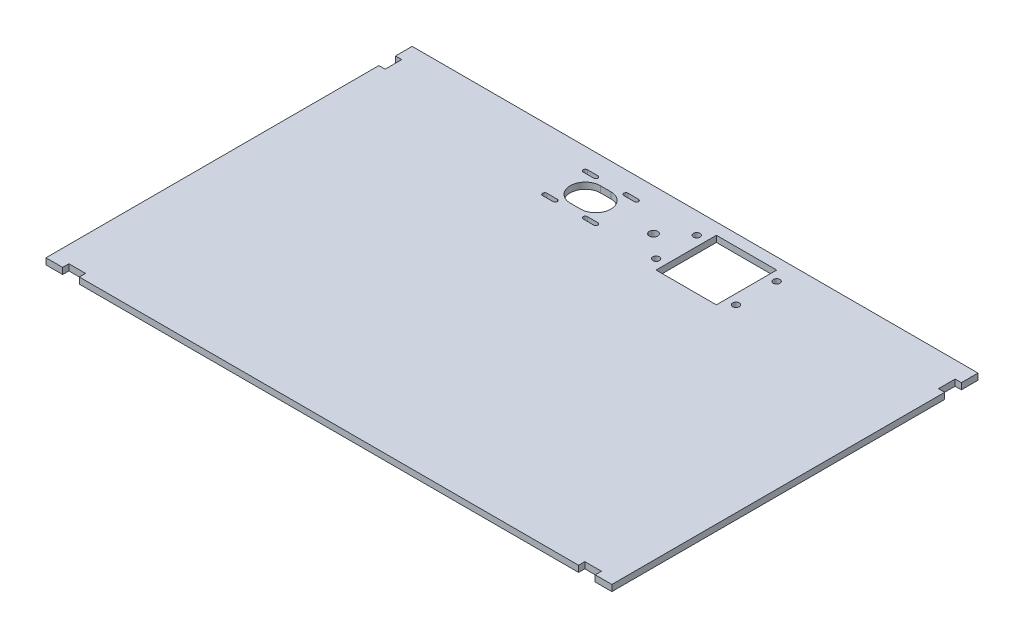
SolidWorks part; units mm, degrees
ref_plane "Front" through (0, 0, 0) normal (0, 0, 1) x (1, 0, 0)
ref_plane "Top" through (0, 0, 0) normal (0, 1, 0) x (1, 0, 0)
ref_plane "Right" through (0, 0, 0) normal (1, 0, 0) x (0, 0, -1)
sketch "Sketch1" plane through (0, 0, 0) normal (0, 1, 0) x (1, 0, 0)
  line L0 (215.9, 247.65) -> (215.9, 279.4) construction
  line L1 (0, 0) -> (12.7, 0)
  line L2 (0, 0) -> (0, 254)
  line L3 (0, 279.4) -> (431.8, 279.4)
  line L4 (431.8, 0) -> (431.8, 254)
  line L5 (148.394, 263.15) -> (156.394, 263.15) construction
  line L6 (148.394, 264.75) -> (156.394, 264.75)
  line L7 (0, 254) -> (4.7625, 254)
  line L8 (431.8, 266.7) -> (427.0375, 266.7)
  line L10 (431.8, 254) -> (427.0375, 254)
  line L11 (427.0375, 266.7) -> (427.0375, 254)
  line L12 (4.7625, 266.7) -> (4.7625, 254)
  line L13 (0, 266.7) -> (4.7625, 266.7)
  line L15 (431.8, 266.7) -> (431.8, 279.4)
  line L16 (0, 266.7) -> (0, 279.4)
  line L17 (25.4, 0) -> (406.4, 0)
  line L19 (12.7, 0) -> (12.7, 4.7625)
  line L20 (12.7, 4.7625) -> (25.4, 4.7625)
  line L21 (25.4, 0) -> (25.4, 4.7625)
  line L22 (406.4, 0) -> (406.4, 4.7625)
  line L23 (419.1, 4.7625) -> (406.4, 4.7625)
  line L24 (419.1, 0) -> (419.1, 4.7625)
  line L25 (419.1, 0) -> (431.8, 0)
  line L26 (167.894, 247.65) -> (215.9, 247.65) construction
  line L27 (152.394, 263.15) -> (183.394, 263.15) construction
  line L28 (152.394, 263.15) -> (152.394, 232.15) construction
  line L29 (152.394, 232.15) -> (183.394, 232.15) construction
  line L30 (183.394, 263.15) -> (183.394, 232.15) construction
  line L31 (152.394, 263.15) -> (183.394, 232.15) construction
  line L32 (152.394, 232.15) -> (183.394, 263.15) construction
  line L33 (248.406, 263.15) -> (279.406, 263.15) construction
  line L34 (248.406, 263.15) -> (248.406, 232.15) construction
  line L35 (248.406, 232.15) -> (279.406, 232.15) construction
  line L36 (279.406, 263.15) -> (279.406, 232.15) construction
  line L37 (248.406, 263.15) -> (279.406, 232.15) construction
  line L38 (248.406, 232.15) -> (279.406, 263.15) construction
  line L39 (215.9, 247.65) -> (263.906, 247.65) construction
  line L40 (148.394, 261.55) -> (156.394, 261.55)
  line L41 (179.394, 263.15) -> (187.394, 263.15) construction
  line L42 (179.394, 264.75) -> (187.394, 264.75)
  line L43 (179.394, 261.55) -> (187.394, 261.55)
  line L44 (148.394, 232.15) -> (156.394, 232.15) construction
  line L45 (148.394, 233.75) -> (156.394, 233.75)
  line L46 (148.394, 230.55) -> (156.394, 230.55)
  line L47 (179.394, 232.15) -> (187.394, 232.15) construction
  line L48 (179.394, 233.75) -> (187.394, 233.75)
  line L49 (179.394, 230.55) -> (187.394, 230.55)
  line L50 (244.406, 263.15) -> (252.406, 263.15) construction
  line L51 (244.406, 264.75) -> (252.406, 264.75)
  line L52 (244.406, 261.55) -> (252.406, 261.55)
  line L53 (244.406, 232.15) -> (252.406, 232.15) construction
  line L54 (244.406, 233.75) -> (252.406, 233.75)
  line L55 (244.406, 230.55) -> (252.406, 230.55)
  line L56 (275.406, 232.15) -> (283.406, 232.15) construction
  line L57 (275.406, 233.75) -> (283.406, 233.75)
  line L58 (275.406, 230.55) -> (283.406, 230.55)
  line L59 (283.406, 263.15) -> (275.406, 263.15) construction
  line L60 (283.406, 261.55) -> (275.406, 261.55)
  line L61 (283.406, 264.75) -> (275.406, 264.75)
  line L62 (163.894, 247.65) -> (171.894, 247.65) construction
  line L63 (163.894, 259.15) -> (171.894, 259.15)
  line L64 (163.894, 236.15) -> (171.894, 236.15)
  line L65 (259.906, 247.65) -> (267.906, 247.65) construction
  line L66 (259.906, 259.15) -> (267.906, 259.15)
  line L67 (259.906, 236.15) -> (267.906, 236.15)
  circle A0 centre (215.9, 247.65) radius 3.175
  arc A12 (148.394, 264.75) -> (148.394, 261.55) centre (148.394, 263.15) ccw
  arc A13 (156.394, 261.55) -> (156.394, 264.75) centre (156.394, 263.15) ccw
  arc A14 (179.394, 264.75) -> (179.394, 261.55) centre (179.394, 263.15) ccw
  arc A15 (187.394, 261.55) -> (187.394, 264.75) centre (187.394, 263.15) ccw
  arc A16 (148.394, 233.75) -> (148.394, 230.55) centre (148.394, 232.15) ccw
  arc A17 (156.394, 230.55) -> (156.394, 233.75) centre (156.394, 232.15) ccw
  arc A18 (179.394, 233.75) -> (179.394, 230.55) centre (179.394, 232.15) ccw
  arc A19 (187.394, 230.55) -> (187.394, 233.75) centre (187.394, 232.15) ccw
  arc A20 (244.406, 264.75) -> (244.406, 261.55) centre (244.406, 263.15) ccw
  arc A21 (252.406, 261.55) -> (252.406, 264.75) centre (252.406, 263.15) ccw
  arc A22 (244.406, 233.75) -> (244.406, 230.55) centre (244.406, 232.15) ccw
  arc A23 (252.406, 230.55) -> (252.406, 233.75) centre (252.406, 232.15) ccw
  arc A24 (275.406, 233.75) -> (275.406, 230.55) centre (275.406, 232.15) ccw
  arc A25 (283.406, 230.55) -> (283.406, 233.75) centre (283.406, 232.15) ccw
  arc A26 (283.406, 261.55) -> (283.406, 264.75) centre (283.406, 263.15) ccw
  arc A27 (275.406, 264.75) -> (275.406, 261.55) centre (275.406, 263.15) ccw
  arc A28 (163.894, 259.15) -> (163.894, 236.15) centre (163.894, 247.65) ccw
  arc A29 (171.894, 236.15) -> (171.894, 259.15) centre (171.894, 247.65) ccw
  arc A30 (259.906, 259.15) -> (259.906, 236.15) centre (259.906, 247.65) ccw
  arc A31 (267.906, 236.15) -> (267.906, 259.15) centre (267.906, 247.65) ccw
  point P19 (183.394, 263.15)
  point P24 (152.394, 263.15)
  point P32 (248.406, 232.15)
  point P44 (12.7, 2.3813)
  point P57 (152.394, 232.15)
  point P64 (183.394, 232.15)
  point P70 (248.406, 263.15)
  point P80 (279.406, 232.15)
  point P87 (279.406, 263.15)
  point P95 (167.894, 247.65)
  point P100 (263.906, 247.65)
  dimension "D4" = 6.35
  dimension "D5" = 1.6
  dimension "D10" = 4
  dimension "D3" = 31.75
  dimension "D9" = 11.5
  dimension "D1" = 279.4
  dimension "D2" = 431.8
  dimension "D6" = 48.006
  dimension "D7" = 48.006
  dimension "D8" = 31
  dimension "D11" = 4
  dimension "D12" = 4.7625
  dimension "D13" = 12.7
  dimension "D14" = 12.7
  dimension "D15" = 4.7625
  dimension "D16" = 12.7
  dimension "D17" = 12.7
extrude "Boss-Extrude1" add sketch "Sketch1" along normal blind 4.7625
sketch "Sketch5" plane through (0, 4.7625, 0) normal (0, 1, 0) x (1, 0, 0)
  line L0 (263.906, 259.15) -> (263.906, 236.15) construction
  line L5 (267.906, 259.15) -> (259.906, 259.15) construction
  line L6 (259.906, 236.15) -> (267.906, 236.15) construction
  line L7 (248.406, 247.65) -> (279.406, 247.65) construction
  line L8 (233.426, 232.15) -> (254.006, 232.15) construction
  line L9 (240.906, 224.65) -> (286.906, 224.65)
  line L10 (240.906, 224.65) -> (240.906, 270.65)
  line L11 (240.906, 270.65) -> (286.906, 270.65)
  line L12 (286.906, 224.65) -> (286.906, 270.65)
  line L13 (240.906, 224.65) -> (286.906, 270.65) construction
  line L14 (240.906, 270.65) -> (286.906, 224.65) construction
  line L15 (254.006, 263.15) -> (233.426, 263.15) construction
  line L17 (225.806, 224.536) -> (302.006, 224.536) construction
  line L18 (225.806, 224.536) -> (225.806, 270.764) construction
  line L19 (225.806, 270.764) -> (302.006, 270.764) construction
  line L20 (302.006, 224.536) -> (302.006, 270.764) construction
  line L21 (225.806, 224.536) -> (302.006, 270.764) construction
  line L22 (225.806, 270.764) -> (302.006, 224.536) construction
  arc A0 (259.906, 259.15) -> (259.906, 236.15) centre (259.906, 247.65) ccw construction
  arc A1 (267.906, 236.15) -> (267.906, 259.15) centre (267.906, 247.65) ccw construction
  circle A2 centre (233.426, 263.15) radius 2.54
  circle A3 centre (294.386, 263.15) radius 2.54
  circle A4 centre (233.426, 232.15) radius 2.54
  circle A5 centre (294.386, 232.15) radius 2.54
  arc A7 (252.406, 230.55) -> (252.406, 233.75) centre (252.406, 232.15) ccw construction
  arc A8 (252.406, 261.55) -> (252.406, 264.75) centre (252.406, 263.15) ccw construction
  point P0 (263.906, 247.65)
  point P32 (0, 0)
  point P33 (263.906, 247.65)
  dimension "D2" = 5.08
  dimension "D1" = 46
  dimension "D3" = 76.2
  dimension "D4" = 46.228
  dimension "D5" = 7.62
  dimension "D6" = 7.62
extrude "Cut-Extrude2" cut sketch "Sketch5" against normal through all
